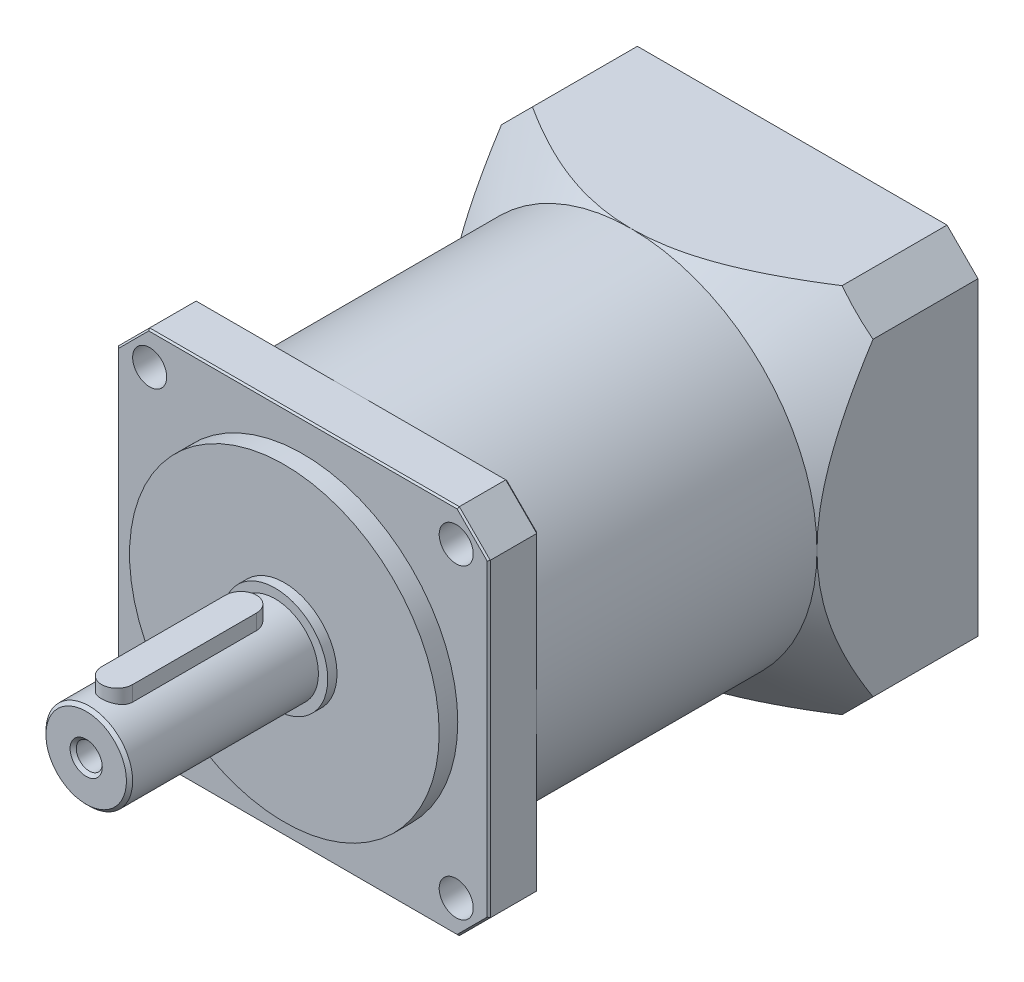
SolidWorks part; units mm, degrees
ref_plane "Спереди" through (0, 0, 0) normal (0, 0, 1) x (1, 0, 0)
ref_plane "Сверху" through (0, 0, 0) normal (0, 1, 0) x (1, 0, 0)
ref_plane "Справа" through (0, 0, 0) normal (1, 0, 0) x (0, 0, -1)
sketch "Эскиз1" plane through (0, 0, 0) normal (0, 0, 1) x (1, 0, 0)
  line L1 (-30, -30) -> (30, -30)
  line L2 (-30, -30) -> (-30, 30)
  line L3 (-30, 30) -> (30, 30)
  line L4 (30, -30) -> (30, 30)
  line L5 (-30, -30) -> (30, 30) construction
  line L6 (-30, 30) -> (30, -30) construction
  point P0 (0, 0)
  dimension "D1" = 60
  dimension "D2" = 60
extrude "Бобышка-Вытянуть1" add sketch "Эскиз1" along normal blind 32
sketch "Эскиз2" plane through (0, 0, 32) normal (0, 0, 1) x (1, 0, 0)
  circle A0 centre (0, 0) radius 30
  dimension "D1" = 60
extrude "Бобышка-Вытянуть2" add sketch "Эскиз2" along normal blind 39
sketch "Эскиз3" plane through (0, 0, 71) normal (0, 0, 1) x (1, 0, 0)
  line L1 (30, -30) -> (-30, -30)
  line L2 (30, -30) -> (30, 30)
  line L3 (30, 30) -> (-30, 30)
  line L4 (-30, -30) -> (-30, 30)
  line L5 (30, -30) -> (-30, 30) construction
  line L6 (30, 30) -> (-30, -30) construction
  point P0 (0, 0)
extrude "Бобышка-Вытянуть3" add sketch "Эскиз3" along normal blind 8
sketch "Эскиз4" plane through (0, 0, 79) normal (0, 0, 1) x (1, 0, 0)
  circle A0 centre (0, 0) radius 25
  dimension "D1" = 50
extrude "Бобышка-Вытянуть4" add sketch "Эскиз4" along normal blind 3
sketch "Эскиз5" plane through (0, 0, 79) normal (0, 0, 1) x (1, 0, 0)
  circle A0 centre (0, 0) radius 7
  dimension "D1" = 14
extrude "Бобышка-Вытянуть5" add sketch "Эскиз5" along normal blind 35
sketch "Эскиз6" plane through (0, 0, 79) normal (0, 0, 1) x (1, 0, 0)
  circle A0 centre (0, 0) radius 8.5
  dimension "D1" = 17
extrude "Бобышка-Вытянуть6" add sketch "Эскиз6" along normal offset from surface (4.5 mm away) 30.5 up to face at (7, 0, 114)
chamfer "Фаска1" distance 5 angle 45 8 edges at (30, 30, 16) (30, 30, 75) (30, -30, 16) (30, -30, 75) (-30, -30, 16) (-30, -30, 75) (-30, 30, 16) (-30, 30, 75)
hole_wizard "Диаметр отверстия Ø5.5 (5.5)1" positions "Эскиз8" profile "Эскиз9" hole size "Ø5.5" standard "ISO"
sketch "Эскиз8" plane through (0, 0, 79) normal (0, 0, 1) x (1, 0, 0)
  line L0 (0, 0) -> (0, 30) construction
  line L2 (0, 0) -> (30, 0) construction
  line L3 (30, -25) -> (30, 25) construction
  point P0 (-24.7487, 24.7487)
  point P14 (24.7487, 24.7487)
  point P15 (24.7487, -24.7487)
  point P16 (-24.7487, -24.7487)
  dimension "D1" = 70
sketch "Эскиз9" plane through (-24.7487, 24.7487, 79) normal (1, 0, 0) x (0, -1, 0)
  line L0 (0, 0) -> (0, 25.6524)
  line L1 (0, 25.6524) -> (2.75, 24)
  line L2 (2.75, 24) -> (2.75, 0)
  line L5 (2.75, 0) -> (0, 0)
  line L10 (0, 25.6524) -> (-2.75, 24) construction
  line L11 (0, -6.35) -> (0, 107.95) construction
  dimension "Диаметр отверстия" = 5.5
  dimension "Глубина отверстия" = 24
  dimension "Угол заточки сверла" = 118
hole_wizard "Отверстие обработанное метчиком M51" positions "Эскиз10" profile "Эскиз12" tap size "M5" standard "ISO"
sketch "Эскиз10" plane through (0, 0, 0) normal (0, 0, -1) x (-1, 0, 0)
  line L0 (0, 0) -> (0, 30) construction
  line L1 (-25, 30) -> (25, 30) construction
  line L3 (0, 0) -> (30, 0) construction
  line L4 (30, 25) -> (30, -25) construction
  point P0 (-23.57, 23.57)
  point P8 (23.57, 23.57)
  point P16 (23.57, -23.57)
  point P17 (-23.57, -23.57)
  dimension "D1" = 47.14
  dimension "D2" = 47.14
sketch "Эскиз12" plane through (23.57, 23.57, 0) normal (1, 0, 0) x (0, 1, 0)
  line L0 (0, 0) -> (0, 16.2618)
  line L1 (0, 16.2618) -> (2.1, 15)
  line L2 (2.1, 15) -> (2.1, 0)
  line L5 (2.1, 0) -> (0, 0)
  line L10 (0, 16.2618) -> (-2.1, 15) construction
  line L11 (0, -6.35) -> (0, 107.95) construction
  dimension "Диаметр сверла" = 4.2
  dimension "Глубина сверла" = 15
  dimension "Угол заточки сверла" = 118
cosmetic thread "Отверстие резьбы1" parameters "D1"=10, "D2"=5
cosmetic thread "Отверстие резьбы2" parameters "D1"=10, "D2"=5
cosmetic thread "Отверстие резьбы3" parameters "D1"=10, "D2"=5
cosmetic thread "Отверстие резьбы4" parameters "D1"=10, "D2"=5
sketch "Эскиз13" plane through (0, 0, 0) normal (1, 0, 0) x (0, 0, -1)
  line L1 (-32, 30) -> (0, 30) construction
  line L2 (-32, 41) -> (-15, 41)
  line L3 (-15, 41) -> (-26, 30)
  line L5 (0, -25) -> (0, 25) construction
  line L6 (0, 0) -> (-114, 0) construction
  line L7 (-114, 7) -> (-114, -7) construction
  line L8 (-26, 30) -> (-32, 30)
  line L9 (-32, 30) -> (-32, 41)
  dimension "D1" = 6
  dimension "D2" = 15
  dimension "D3" = 45
revolve "Вырез-Повернуть1" cut sketch "Эскиз13" angle 360 about L6
sketch "Эскиз14" plane through (0, 0, 0) normal (0, 1, 0) x (1, 0, 0)
  line L0 (0, -114) -> (0, -83.5) construction
  line L1 (-7, -114) -> (7, -114) construction
  line L2 (-7, -83.5) -> (7, -83.5) construction
  line L3 (0, -89) -> (0, -109) construction
  line L4 (2.5, -89) -> (2.5, -109)
  line L5 (-2.5, -89) -> (-2.5, -109)
  arc A0 (2.5, -89) -> (-2.5, -89) centre (0, -89) ccw
  arc A1 (-2.5, -109) -> (2.5, -109) centre (0, -109) ccw
  point P8 (0, -99)
  point P13 (0, -111.5)
  dimension "D1" = 5
  dimension "D2" = 25
  dimension "D3" = 2.5
extrude "Бобышка-Вытянуть7" add sketch "Эскиз14" along normal blind 9
chamfer "Фаска2" distance 0.5 angle 45 1 edges at (7, 0, 114)
hole_wizard "Отверстие обработанное метчиком M52" positions "Эскиз15" profile "Эскиз16" tap size "M5" standard "ISO"
sketch "Эскиз15" plane through (0, 0, 114) normal (0, 0, 1) x (1, 0, 0)
  point P0 (0, 0)
sketch "Эскиз16" plane through (0, 0, 114) normal (1, 0, 0) x (0, -1, 0)
  line L0 (0, 0) -> (0, 16.2618)
  line L1 (0, 16.2618) -> (2.1, 15)
  line L2 (2.1, 15) -> (2.1, 0)
  line L5 (2.1, 0) -> (0, 0)
  line L10 (0, 16.2618) -> (-2.1, 15) construction
  line L11 (0, -6.35) -> (0, 107.95) construction
  dimension "Диаметр сверла" = 4.2
  dimension "Глубина сверла" = 15
  dimension "Угол заточки сверла" = 118
cosmetic thread "Отверстие резьбы5" parameters "D1"=10, "D2"=5
chamfer "Фаска3" distance 0.5 angle 45 1 edges at (2.1, 0, 114)
chamfer "Фаска4" distance 0.25 angle 45 20 edges at (-30, 12.5, 71) (-30, -12.5, 71) (-27.5, -27.5, 71) (-12.5, -30, 71) (12.5, -30, 71) (27.5, -27.5, 71) (30, -12.5, 71) (30, 12.5, 71) (27.5, 27.5, 71) (12.5, 30, 71) (-12.5, 30, 71) (-27.5, 27.5, 71) (-27.5, 27.5, 79) (-30, 0, 79) (-27.5, -27.5, 79) (0, -30, 79) (27.5, -27.5, 79) (30, 0, 79) (27.5, 27.5, 79) (0, 30, 79)
